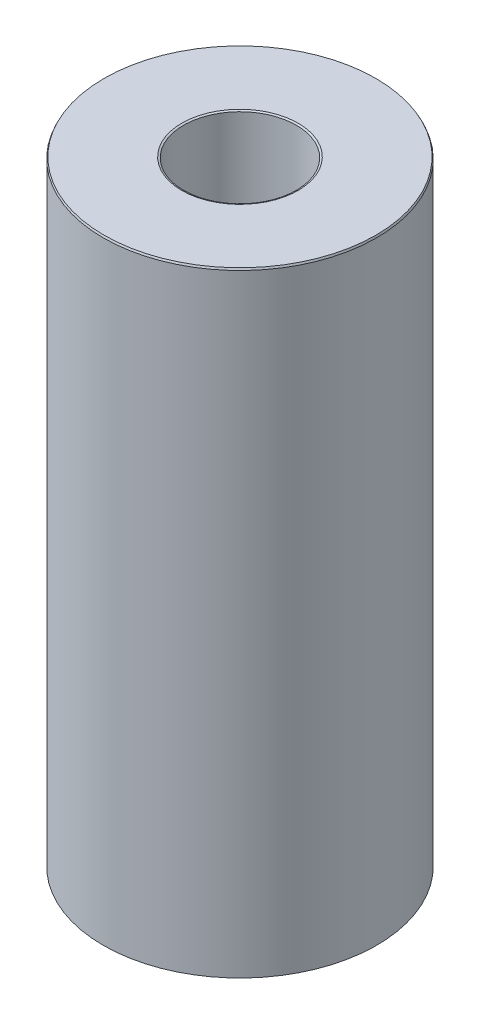
SolidWorks part; units mm, degrees
ref_plane "Front Plane" through (0, 0, 0) normal (0, 0, 1) x (1, 0, 0)
ref_plane "Top Plane" through (0, 0, 0) normal (0, 1, 0) x (1, 0, 0)
ref_plane "Right Plane" through (0, 0, 0) normal (1, 0, 0) x (0, 0, -1)
sketch "Sketch1" plane through (0, 0, 0) normal (0, 1, 0) x (1, 0, 0)
  circle A0 centre (0, 0) radius 50
  dimension "SLEEVE_OD" = 100
extrude "Boss-Extrude1" add sketch "Sketch1" along normal blind 225.1241
sketch "Sketch2" plane through (0, 0, 0) normal (0, 1, 0) x (1, 0, 0)
  circle A0 centre (0, 0) radius 20.6365
  dimension "BORE_D" = 41.2731
extrude "Cut-Extrude1" cut sketch "Sketch2" along normal through all
chamfer "Chamfer1" distance 0.6678 angle 23.998 4 edges at (0, 225.1241, 20.6365) (0, 0, 20.6365) (0, 0, 50) (0, 225.1241, 50) first distance on face at (0, 225.1241, 20.6365) first distance on face at (0, 0, 20.6365) first distance on face at (0, 225.1241, 50)
